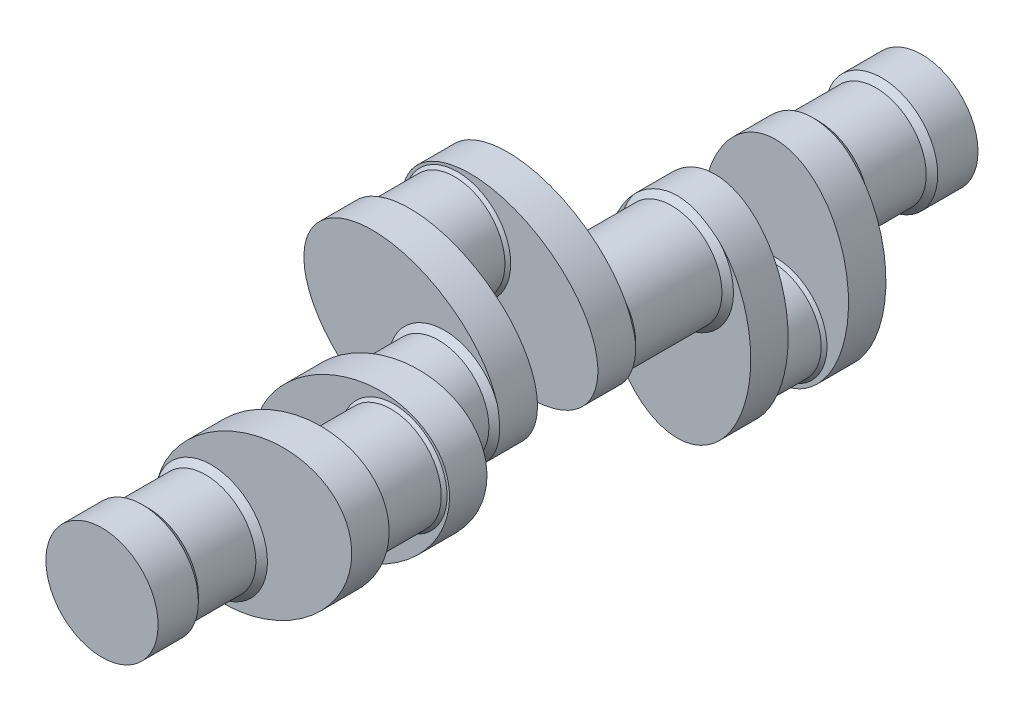
SolidWorks part; units mm, degrees
ref_plane "Front Plane" through (0, 0, 0) normal (0, 0, 1) x (1, 0, 0)
ref_plane "Top Plane" through (0, 0, 0) normal (0, 1, 0) x (1, 0, 0)
ref_plane "Right Plane" through (0, 0, 0) normal (1, 0, 0) x (0, 0, -1)
sketch "Sketch1" plane through (0, 0, 0) normal (0, 0, 1) x (1, 0, 0)
  circle A0 centre (0, 0) radius 19.5
  dimension "D1" = 39
extrude "Boss-Extrude2" add sketch "Sketch1" along normal blind 14
sketch "Sketch3" plane through (0, 0, 0) normal (0, 0, 1) x (1, 0, 0)
  circle A0 centre (0, 0) radius 17.5
  dimension "D1" = 35
extrude "Boss-Extrude3" add sketch "Sketch3" along normal blind 24 from surface starting at face at (19.5, 0, 14)
sketch "Sketch4" plane through (0, 0, 0) normal (0, 0, 1) x (1, 0, 0)
  line L0 (0, 0) -> (-38.5305, 0) construction
  line L1 (-38.5305, 0) -> (-38.5305, -17) construction
  line L2 (-38.5305, -17) -> (1.014, -17) construction
  line L3 (1.014, -17) -> (1.014, 1.1022) construction
  line L4 (1.014, 1.1022) -> (1.014, 17) construction
  line L5 (1.014, 17) -> (-38.5305, 17) construction
  line L6 (-38.5305, 17) -> (-38.5305, 0) construction
  circle A0 centre (0, 0) radius 19.5 construction
  ellipse E0 centre (0, -17) end of major axis (0, 19.5) minor radius 25.5
  dimension "D1" = 17
  dimension "D2" = 17
  dimension "D3" = 51
extrude "Boss-Extrude5" add sketch "Sketch4" along normal blind 13 from surface starting at face at (17.5, 0, 38)
chamfer "Chamfer2" distance 2 angle 45 1 edges at (17.5, 0, 38)
chamfer "Chamfer3" distance 2 angle 45 1 edges at (17.5, 0, 14)
sketch "Sketch6" plane through (0, 0, 51) normal (0, 0, 1) x (1, 0, 0)
  line L0 (0, 0) -> (0, -63.811) construction
  line L1 (0, 0) -> (-58.6322, 0) construction
  line L2 (0, -17) -> (-58.6322, -17) construction
  line L3 (0, -53.5) -> (-58.6322, -53.5) construction
  line L4 (0, -34) -> (-58.6322, -34) construction
  circle A2 centre (0, -34) radius 17
  spline S0 degree 3 poles (0, 19.5) (-51, 19.5) (-51, -53.5) (0, -53.5) (51, -53.5) (51, 19.5) (0, 19.5) (-51, 19.5) (-51, -53.5) knots -0.5 0 0 0 0.5 0.5 0.5 1 1 1 1.5 1.5 1.5 weights 1 0.333333 0.333333 1 0.333333 0.333333 1 0.333333 0.333333 only from (0, 19.5) to (0, 19.5) construction
  dimension "D1" = 17
  dimension "D2" = 17
  dimension "D3" = 19.5
extrude "Boss-Extrude6" add sketch "Sketch6" along normal blind 21
sketch "Sketch7" plane through (0, 0, 72) normal (0, 0, 1) x (1, 0, 0)
  circle A0 centre (0, -34) radius 17 construction
  ellipse E0 centre (0, -17) end of major axis (0, -53.5) minor radius 25.5
  spline S0 degree 3 poles (0, 19.5) (-51, 19.5) (-51, -53.5) (0, -53.5) (51, -53.5) (51, 19.5) (0, 19.5) (-51, 19.5) (-51, -53.5) knots -0.5 0 0 0 0.5 0.5 0.5 1 1 1 1.5 1.5 1.5 weights 1 0.333333 0.333333 1 0.333333 0.333333 1 0.333333 0.333333 only from (0, 19.5) to (0, 19.5) construction
extrude "Boss-Extrude7" add sketch "Sketch7" along normal blind 13
sketch "Sketch8" plane through (0, 0, 85) normal (0, 0, 1) x (1, 0, 0)
  line L0 (0, -17) -> (-48.8349, -17) construction
  line L4 (0, -17) -> (0, 19.5) construction
  line L5 (0, 19.5) -> (-48.8349, 19.5) construction
  line L6 (-48.8349, 19.5) -> (-48.8349, -17) construction
  line L7 (-48.8349, 1.25) -> (0, 1.25) construction
  point P10 (0, 0)
chamfer "Chamfer4" distance 1 angle 45 1 edges at (-17, -34, 51)
chamfer "Chamfer5" distance 1 angle 45 1 edges at (17, -34, 72)
sketch "Sketch10" plane through (0, 0, 0) normal (1, 0, 0) x (0, 0, -1)
  line L0 (0, 0) -> (-305.1641, 0) construction
sketch "Sketch11" plane through (0, 0, 85) normal (0, 0, 1) x (1, 0, 0)
  circle A1 centre (0, 0) radius 17.5
extrude "Boss-Extrude8" add sketch "Sketch11" along normal blind 34
sketch "Sketch13" plane through (0, 0, 119) normal (0, 0, 1) x (1, 0, 0)
  line L0 (0, 0) -> (-14.7224, 8.5) construction
  ellipse E0 centre (-14.7224, 8.5) end of major axis (16.8875, -9.75) minor radius 25.5
extrude "Boss-Extrude9" add sketch "Sketch13" along normal blind 13
sketch "Sketch15" plane through (0, 0, 132) normal (0, 0, 1) x (1, 0, 0)
  line L0 (0, 0) -> (-29.4449, 17) construction
  circle A0 centre (-29.4449, 17) radius 17.5
extrude "Boss-Extrude10" add sketch "Sketch15" along normal blind 21
sketch "Sketch20" plane through (0, 0, 153) normal (0, 0, 1) x (1, 0, 0)
  line L0 (-29.4449, 17) -> (-14.7224, 8.5) construction
  ellipse E0 centre (-14.7224, 8.5) end of major axis (-46.3324, 26.75) minor radius 25.5
  point P0 (-29.4449, 17)
extrude "Boss-Extrude11" add sketch "Sketch20" along normal blind 13
sketch "Sketch21" plane through (0, 0, 166) normal (0, 0, 1) x (1, 0, 0)
  circle A0 centre (0, 0) radius 17.5
extrude "Boss-Extrude12" add sketch "Sketch21" along normal blind 34
sketch "Sketch22" plane through (0, 0, 200) normal (0, 0, 1) x (1, 0, 0)
  line L0 (0, 0) -> (14.7224, 8.5) construction
  ellipse E0 centre (14.7224, 8.5) end of major axis (-16.8875, -9.75) minor radius 25.5
extrude "Boss-Extrude13" add sketch "Sketch22" along normal blind 13
chamfer "Chamfer6" distance 2 angle 45 4 edges at (17.5, 0, 200) (17.5, 0, 166) (17.5, 0, 119) (17.5, 0, 85)
sketch "Sketch27" plane through (0, 0, 213) normal (0, 0, 1) x (1, 0, 0)
  line L0 (0, 0) -> (29.4449, 17) construction
  circle A0 centre (29.4449, 17) radius 17.5
extrude "Boss-Extrude18" add sketch "Sketch27" along normal blind 21
sketch "Sketch32" plane through (0, 0, 234) normal (0, 0, 1) x (1, 0, 0)
  line L0 (29.4449, 17) -> (14.7224, 8.5) construction
  ellipse E0 centre (14.7224, 8.5) end of major axis (46.3324, 26.75) minor radius 25.5
extrude "Boss-Extrude19" add sketch "Sketch32" along normal blind 13
sketch "Sketch33" plane through (0, 0, 247) normal (0, 0, 1) x (1, 0, 0)
  circle A0 centre (0, 0) radius 17.5
extrude "Boss-Extrude20" add sketch "Sketch33" along normal blind 24
sketch "Sketch34" plane through (0, 0, 271) normal (0, 0, 1) x (1, 0, 0)
  circle A0 centre (0, 0) radius 19.5
extrude "Boss-Extrude21" add sketch "Sketch34" along normal blind 14
chamfer "Chamfer7" distance 2 angle 45 2 edges at (17.5, 0, 271) (17.5, 0, 247)
chamfer "Chamfer8" distance 1 angle 45 4 edges at (-11.9449, 17, 132) (-11.9449, 17, 153) (46.9449, 17, 234) (46.9449, 17, 213)
